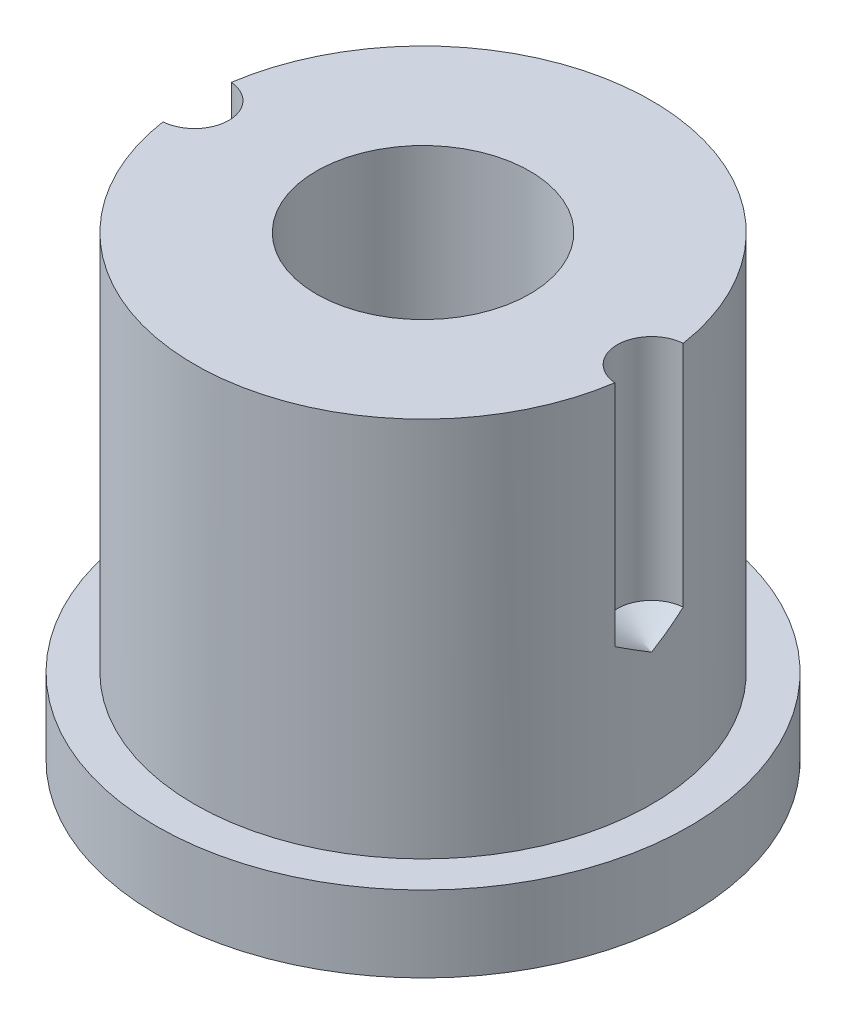
SolidWorks part; units mm, degrees
material "Commercial Bronze, UNS C22000 (90-10 Bronze)"
ref_plane "Front Plane" through (0, 0, 0) normal (0, 0, 1) x (1, 0, 0)
ref_plane "Top Plane" through (0, 0, 0) normal (0, 1, 0) x (1, 0, 0)
ref_plane "Right Plane" through (0, 0, 0) normal (1, 0, 0) x (0, 0, -1)
sketch "Sketch1" plane through (0, 0, 0) normal (0, 1, 0) x (1, 0, 0)
  circle A0 centre (0, 0) radius 35
  dimension "D1" = 70
extrude "Boss-Extrude1" add sketch "Sketch1" along normal blind 10
sketch "Sketch2" plane through (0, 10, 0) normal (0, 1, 0) x (1, 0, 0)
  circle A0 centre (0, 0) radius 30
  dimension "D1" = 60
extrude "Boss-Extrude2" add sketch "Sketch2" along normal blind 50
sketch "Sketch3" plane through (0, 60, 0) normal (0, 1, 0) x (1, 0, 0)
  circle A0 centre (0, 0) radius 14
  dimension "D1" = 28
extrude "Cut-Extrude1" cut sketch "Sketch3" against normal through all
hole_wizard "Ø8.0mm Dowel Hole1" positions "Sketch4" profile "Sketch5" hole size "Ø8.0" standard "ISO"
sketch "Sketch4" plane through (0, 60, 0) normal (0, 1, 0) x (1, 0, 0)
  circle A0 centre (0, 0) radius 30 construction
  circle A1 centre (0, 0) radius 30 construction
  point P0 (-30, 0)
  point P4 (30, 0)
sketch "Sketch5" plane through (-30, 60, 0) normal (1, 0, 0) x (0, 0, 1)
  line L0 (0, 0) -> (0, 32.7039)
  line L1 (0, 32.7039) -> (4.5, 30)
  line L2 (4.5, 30) -> (4.5, 0)
  line L5 (4.5, 0) -> (0, 0)
  line L10 (0, 32.7039) -> (-4.5, 30) construction
  line L11 (0, -6.35) -> (0, 107.95) construction
  dimension "Hole Dia." = 9
  dimension "Hole Depth" = 30
  dimension "Drill Angle" = 118
